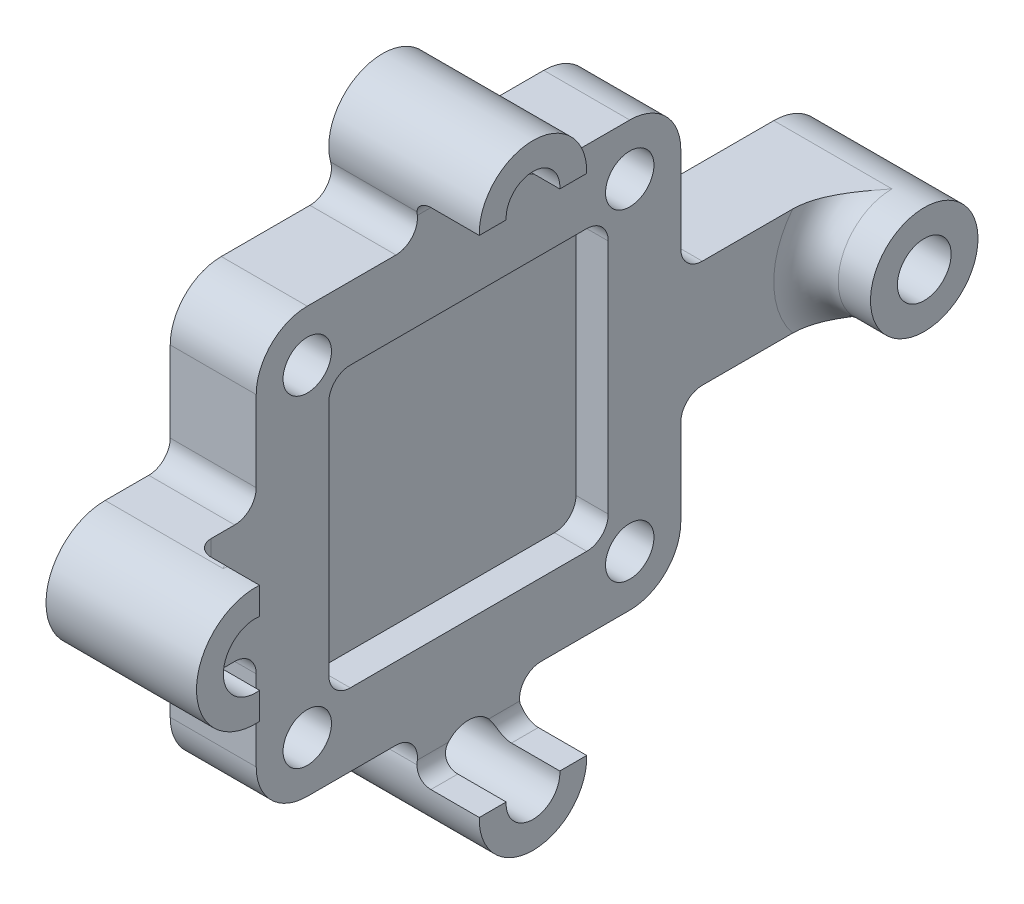
SolidWorks part; units mm, degrees
material "Beryllium S-65C, Vacuum Hot Pressed"
ref_plane "Front Plane" through (0, 0, 0) normal (1, 0, 0) x (0, 1, 0)
ref_plane "Top Plane" through (0, 0, 0) normal (0, 0, 1) x (0, 1, 0)
ref_plane "Right Plane" through (0, 0, 0) normal (0, 1, 0) x (-1, 0, 0)
sketch "Sketch1" plane through (0, 0, 0) normal (1, 0, 0) x (0, 1, 0)
sketch "Model" plane through (0, 0, 0) normal (1, 0, 0) x (0, 1, 0)
  line L0 (7, -36.4) -> (7, -53.9815)
  line L1 (-7, -36.4) -> (-7, -53.9815)
  line L2 (-7, -53.9815) -> (7, -53.9815)
  line L3 (7, -53.9815) -> (36.1014, -41.334)
  line L4 (0, 0) -> (0, -59.9211) construction
  line L5 (-7, -53.9815) -> (-36.1014, -41.334)
  line L6 (-15.7213, -20.9539) -> (-36.1014, -41.334)
  line L7 (-15.7213, -20.9539) -> (-7, -36.4)
  line L8 (15.7213, -20.9539) -> (7, -36.4)
  line L9 (36.1014, -41.334) -> (15.7213, -20.9539)
  line L10 (9.3322, 8.6384) -> (11.3322, 8.6384)
  line L11 (5.3322, 14.6384) -> (5.3322, 12.6384)
  line L12 (-5.3322, 14.6384) -> (-5.3322, 12.6384)
  line L13 (-11.3322, 8.6384) -> (-9.3322, 8.6384)
  line L14 (9.3322, -11.4697) -> (11.3322, -11.4697)
  line L15 (8.703, -13.6232) -> (10.3884, -14.7)
  line L16 (-5.3322, 14.6384) -> (5.3322, 14.6384)
  line L17 (5.3322, 12.6384) -> (-5.3322, 12.6384)
  line L18 (9.3322, -11.4697) -> (9.3322, 8.6384)
  line L19 (11.3322, 8.6384) -> (11.3322, -11.4697)
  line L20 (-5.0562, -23.046) -> (-10.3884, -14.7)
  line L21 (-10.3884, -14.7) -> (-8.703, -13.6232)
  line L22 (-8.703, -13.6232) -> (-3.3708, -21.9692)
  line L23 (-3.3708, -21.9692) -> (-5.0562, -23.046)
  line L24 (3.3708, -21.9692) -> (8.703, -13.6232)
  line L25 (10.3884, -14.7) -> (5.0562, -23.046)
  line L26 (3.3708, -21.9692) -> (5.0562, -23.046)
  line L27 (-11.3322, -11.4697) -> (-11.3322, 8.6384)
  line L28 (-9.3322, 8.6384) -> (-9.3322, -11.4697)
  line L29 (-11.3322, -11.4697) -> (-9.3322, -11.4697)
  line L30 (-7.1532, 23.5517) -> (-11.8182, 18.8569)
  line L31 (7, -36.4) -> (16.3675, -19.8094)
  line L32 (19.8245, -13.6868) -> (23.6, -7)
  line L33 (-23.6, -7) -> (-19.8245, -13.6868)
  line L34 (11.8182, 18.8569) -> (7.1532, 23.5517)
  line L35 (23.6, 7) -> (18.8366, 11.7937)
  line L36 (-16.3675, -19.8094) -> (-7, -36.4)
  line L37 (-18.8366, 11.7937) -> (-23.6, 7)
  line L38 (42.1215, -47.354) -> (36.1014, -41.334)
  line L39 (36.1014, -41.334) -> (9.7972, -52.7658)
  line L40 (7, -50.9316) -> (7, -36.4)
  line L41 (26.4236, -41.1785) -> (13.7972, -46.666)
  line L42 (18.4772, -29.3667) -> (27.0406, -37.93)
  line L43 (11.2584, -36.9935) -> (15.3215, -29.7976)
  line L44 (11, -44.8317) -> (11, -37.9769)
  line L45 (23.4176, -18.185) -> (47.354, -42.1215)
  line L46 (-36.1014, -41.334) -> (-42.1215, -47.354)
  line L47 (-7, -50.9316) -> (-7, -36.4)
  line L48 (-36.1014, -41.334) -> (-9.7972, -52.7658)
  line L49 (-11, -37.9769) -> (-11, -44.8317)
  line L50 (-15.3215, -29.7976) -> (-11.2584, -36.9935)
  line L51 (-27.0406, -37.93) -> (-18.4772, -29.3667)
  line L52 (-13.7972, -46.666) -> (-26.4236, -41.1785)
  line L53 (-47.354, -42.1215) -> (-23.4176, -18.185)
  line L54 (-23.4176, 18.185) -> (-47.354, 42.1215)
  line L55 (-42.1215, 47.354) -> (-18.185, 23.4176)
  line L56 (18.185, 23.4176) -> (42.1215, 47.354)
  line L57 (47.354, 42.1215) -> (23.4176, 18.185)
  line L58 (-26.9652, 35.0583) -> (-27.1076, 34.9484)
  line L59 (-32.6677, 40.7516) -> (-32.7868, 40.6559)
  line L60 (32.7803, 40.6611) -> (32.6631, 40.7553)
  line L61 (27.1112, 34.9456) -> (26.9658, 35.0579)
  line L62 (-33.8602, 41.9421) -> (-32.6677, 40.7516)
  line L63 (32.6631, 40.7553) -> (33.8545, 41.9467)
  arc A0 (-7, -36.4) -> (7, -36.4) centre (0, -36.4) ccw
  circle A1 centre (-15, -15) radius 2.25
  circle A2 centre (23.6, 0) radius 3
  circle A3 centre (0, -36.4) radius 3
  circle A4 centre (-15, 15) radius 2.25
  circle A5 centre (0, 25.8061) radius 3.5
  circle A6 centre (15, -15) radius 2.25
  circle A7 centre (15, 15) radius 2.25
  circle A8 centre (-23.6, 0) radius 3
  circle A9 centre (49.4975, -49.4975) radius 3
  circle A10 centre (53.9975, -49.4975) radius 1.25
  circle A11 centre (49.4975, -44.9975) radius 1.25
  circle A12 centre (49.4975, -53.9975) radius 1.25
  circle A13 centre (44.9975, -49.4975) radius 1.25
  circle A14 centre (-49.4975, -49.4975) radius 3
  circle A15 centre (-44.9975, -49.4975) radius 1.25
  circle A16 centre (-53.9975, -49.4975) radius 1.25
  circle A17 centre (-49.4975, -44.9975) radius 1.25
  circle A18 centre (-49.4975, -53.9975) radius 1.25
  circle A19 centre (-49.4975, 49.4975) radius 3
  circle A20 centre (-53.9975, 49.4975) radius 1.25
  circle A21 centre (-49.4975, 44.9975) radius 1.25
  circle A22 centre (-49.4975, 53.9975) radius 1.25
  circle A23 centre (-44.9975, 49.4975) radius 1.25
  circle A24 centre (49.4975, 49.4975) radius 3
  circle A25 centre (49.4975, 53.9975) radius 1.25
  circle A26 centre (44.9975, 49.4975) radius 1.25
  circle A27 centre (53.9975, 49.4975) radius 1.25
  circle A28 centre (49.4975, 44.9975) radius 1.25
  arc A29 (-11.8182, 18.8569) -> (-18.8366, 11.7937) centre (-15, 15) ccw
  arc A30 (-18.185, 23.4176) -> (-23.4176, 18.185) centre (-15, 15) ccw
  arc A31 (-19.8245, -13.6868) -> (-16.3675, -19.8094) centre (-15, -15) ccw
  arc A32 (-23.4176, -18.185) -> (-18.185, -23.4176) centre (-15, -15) ccw
  arc A33 (18.8366, 11.7937) -> (11.8182, 18.8569) centre (15, 15) ccw
  arc A34 (23.4176, 18.185) -> (18.185, 23.4176) centre (15, 15) ccw
  arc A35 (16.3675, -19.8094) -> (19.8245, -13.6868) centre (15, -15) ccw
  arc A36 (18.185, -23.4176) -> (23.4176, -18.185) centre (15, -15) ccw
  arc A37 (11.3322, 8.6384) -> (5.3322, 14.6384) centre (5.3322, 8.6384) ccw
  arc A38 (9.3322, 8.6384) -> (5.3322, 12.6384) centre (5.3322, 8.6384) ccw
  arc A39 (-5.3322, 14.6384) -> (-11.3322, 8.6384) centre (-5.3322, 8.6384) ccw
  arc A40 (-5.3322, 12.6384) -> (-9.3322, 8.6384) centre (-5.3322, 8.6384) ccw
  arc A41 (8.703, -13.6232) -> (9.3322, -11.4697) centre (5.3322, -11.4697) ccw
  arc A42 (10.3884, -14.7) -> (11.3322, -11.4697) centre (5.3322, -11.4697) ccw
  arc A43 (-3.3708, -21.9692) -> (3.3708, -21.9692) centre (0, -19.8157) ccw
  arc A44 (-5.0562, -23.046) -> (5.0562, -23.046) centre (0, -19.8157) ccw
  arc A45 (-11.3322, -11.4697) -> (-10.3884, -14.7) centre (-5.3322, -11.4697) ccw
  arc A46 (7.1532, 23.5517) -> (-7.1532, 23.5517) centre (0, 25.8061) ccw
  arc A47 (23.6, -7) -> (23.6, 7) centre (23.6, 0) ccw
  arc A48 (-23.6, 7) -> (-23.6, -7) centre (-23.6, 0) ccw
  arc A49 (-7, -36.4) -> (7, -36.4) centre (0, -36.4) ccw
  arc A50 (-9.3322, -11.4697) -> (-8.703, -13.6232) centre (-5.3322, -11.4697) ccw
  arc A51 (52.4421, -44.2698) -> (47.777, -42.4994) centre (49.4975, -44.9975) ccw
  arc A52 (54.5148, -46.2072) -> (52.4421, -44.2698) centre (49.4975, -49.4975) ccw
  arc A53 (54.5148, -52.7878) -> (54.5148, -46.2072) centre (53.9975, -49.4975) ccw
  arc A54 (52.4421, -54.7252) -> (54.5148, -52.7878) centre (49.4975, -49.4975) ccw
  arc A55 (46.5528, -54.7252) -> (52.4421, -54.7252) centre (49.4975, -53.9975) ccw
  arc A56 (44.4801, -52.7878) -> (46.5528, -54.7252) centre (49.4975, -49.4975) ccw
  arc A57 (42.3007, -47.5427) -> (44.4801, -52.7878) centre (44.9975, -49.4975) ccw
  arc A58 (7, -50.9316) -> (9.7972, -52.7658) centre (9, -50.9316) ccw
  arc A59 (11, -44.8317) -> (13.7972, -46.666) centre (13, -44.8317) ccw
  arc A60 (26.4236, -41.1785) -> (27.0406, -37.93) centre (25.6264, -39.3443) ccw
  arc A61 (18.4772, -29.3667) -> (15.3215, -29.7976) centre (17.063, -30.7809) ccw
  arc A62 (11.2584, -36.9935) -> (11, -37.9769) centre (13, -37.9769) ccw
  arc A63 (-44.2698, -52.4421) -> (-42.4994, -47.777) centre (-44.9975, -49.4975) ccw
  arc A64 (-46.2072, -54.5148) -> (-44.2698, -52.4421) centre (-49.4975, -49.4975) ccw
  arc A65 (-52.7878, -54.5148) -> (-46.2072, -54.5148) centre (-49.4975, -53.9975) ccw
  arc A66 (-54.7252, -52.4421) -> (-52.7878, -54.5148) centre (-49.4975, -49.4975) ccw
  arc A67 (-54.7252, -46.5528) -> (-54.7252, -52.4421) centre (-53.9975, -49.4975) ccw
  arc A68 (-52.7878, -44.4801) -> (-54.7252, -46.5528) centre (-49.4975, -49.4975) ccw
  arc A69 (-9.7972, -52.7658) -> (-7, -50.9316) centre (-9, -50.9316) ccw
  arc A70 (-13.7972, -46.666) -> (-11, -44.8317) centre (-13, -44.8317) ccw
  arc A71 (-11, -37.9769) -> (-11.2584, -36.9935) centre (-13, -37.9769) ccw
  arc A72 (-15.3215, -29.7976) -> (-18.4772, -29.3667) centre (-17.063, -30.7809) ccw
  arc A73 (-27.0406, -37.93) -> (-26.4236, -41.1785) centre (-25.6264, -39.3443) ccw
  arc A74 (-47.5427, -42.3007) -> (-52.7878, -44.4801) centre (-49.4975, -44.9975) ccw
  arc A75 (-52.4421, 44.2698) -> (-47.777, 42.4994) centre (-49.4975, 44.9975) ccw
  arc A76 (-54.5148, 46.2072) -> (-52.4421, 44.2698) centre (-49.4975, 49.4975) ccw
  arc A77 (-54.5148, 52.7878) -> (-54.5148, 46.2072) centre (-53.9975, 49.4975) ccw
  arc A78 (-52.4421, 54.7252) -> (-54.5148, 52.7878) centre (-49.4975, 49.4975) ccw
  arc A79 (-46.5528, 54.7252) -> (-52.4421, 54.7252) centre (-49.4975, 53.9975) ccw
  arc A80 (-44.4801, 52.7878) -> (-46.5528, 54.7252) centre (-49.4975, 49.4975) ccw
  arc A81 (-42.3007, 47.5427) -> (-44.4801, 52.7878) centre (-44.9975, 49.4975) ccw
  arc A82 (44.2698, 52.4421) -> (42.4994, 47.777) centre (44.9975, 49.4975) ccw
  arc A83 (46.2072, 54.5148) -> (44.2698, 52.4421) centre (49.4975, 49.4975) ccw
  arc A84 (52.7878, 54.5148) -> (46.2072, 54.5148) centre (49.4975, 53.9975) ccw
  arc A85 (54.7252, 52.4421) -> (52.7878, 54.5148) centre (49.4975, 49.4975) ccw
  arc A86 (54.7252, 46.5528) -> (54.7252, 52.4421) centre (53.9975, 49.4975) ccw
  arc A87 (52.7878, 44.4801) -> (54.7252, 46.5528) centre (49.4975, 49.4975) ccw
  arc A88 (47.5427, 42.3007) -> (52.7878, 44.4801) centre (49.4975, 44.9975) ccw
  arc A89 (35.2957, 40.7414) -> (-35.3032, 40.7349) centre (0, 0) ccw
  arc A90 (28.3951, 36.4807) -> (-28.3922, 36.483) centre (0, 0) ccw
  arc A91 (26.9658, 35.0579) -> (-26.9652, 35.0583) centre (0, 0) ccw
  arc A92 (32.432, 40.5241) -> (-32.4363, 40.5206) centre (0, 0) ccw
  spline S0 degree 2 poles (-19.9943, 14.7617) (-20.0274, 14.7948) (-20.0882, 14.8556) knots 0 0 0 0.125 0.125 0.125
  spline S1 degree 3 poles (-20.0882, 14.8556) (-20.1186, 14.886) (-20.1563, 14.9237) (-20.1994, 14.9668) knots 0.125 0.125 0.125 0.125 0.1875 0.1875 0.1875 0.1875
  spline S2 degree 3 poles (-20.1994, 14.9668) (-20.2425, 15.0099) (-20.291, 15.0584) (-20.3442, 15.1116) knots 0.1875 0.1875 0.1875 0.1875 0.25 0.25 0.25 0.25
  spline S3 degree 3 poles (-20.3442, 15.1116) (-20.4505, 15.2179) (-20.5767, 15.3441) (-20.7142, 15.4816) knots 0.25 0.25 0.25 0.25 0.375 0.375 0.375 0.375
  spline S4 degree 3 poles (-20.7142, 15.4816) (-20.8516, 15.6191) (-21.0009, 15.7683) (-21.1609, 15.9283) knots 0.375 0.375 0.375 0.375 0.5 0.5 0.5 0.5
  spline S5 degree 3 poles (-21.1609, 15.9283) (-21.3208, 16.0882) (-21.4929, 16.2603) (-21.6705, 16.438) knots 0.5 0.5 0.5 0.5 0.625 0.625 0.625 0.625
  spline S6 degree 3 poles (-21.6705, 16.438) (-21.8482, 16.6156) (-22.0322, 16.7996) (-22.2228, 16.9902) knots 0.625 0.625 0.625 0.625 0.75 0.75 0.75 0.75
  spline S7 degree 3 poles (-22.2228, 16.9902) (-22.4133, 17.1807) (-22.6118, 17.3792) (-22.8116, 17.579) knots 0.75 0.75 0.75 0.75 0.875 0.875 0.875 0.875
  spline S8 degree 3 poles (-22.8116, 17.579) (-23.0113, 17.7787) (-23.2133, 17.9807) (-23.4176, 18.185) knots 0.875 0.875 0.875 0.875 1 1 1 1
  spline S9 degree 3 poles (-18.185, 23.4176) (-17.776, 23.0086) (-17.3796, 22.6122) (-16.9943, 22.2269) knots 0 0 0 0 0.25 0.25 0.25 0.25
  spline S10 degree 3 poles (-16.9943, 22.2269) (-16.6091, 21.8417) (-16.2547, 21.4873) (-15.9312, 21.1638) knots 0.25 0.25 0.25 0.25 0.5 0.5 0.5 0.5
  spline S11 degree 3 poles (-15.9312, 21.1638) (-15.7694, 21.002) (-15.6199, 20.8525) (-15.4833, 20.7159) knots 0.5 0.5 0.5 0.5 0.625 0.625 0.625 0.625
  spline S12 degree 3 poles (-15.4833, 20.7159) (-15.3468, 20.5794) (-15.223, 20.4556) (-15.1156, 20.3482) knots 0.625 0.625 0.625 0.625 0.75 0.75 0.75 0.75
  spline S13 degree 3 poles (-15.1156, 20.3482) (-15.0081, 20.2407) (-14.9194, 20.152) (-14.8577, 20.0903) knots 0.75 0.75 0.75 0.75 0.875 0.875 0.875 0.875
  spline S14 degree 2 poles (-14.8577, 20.0903) (-14.7961, 20.0287) (-14.7617, 19.9943) knots 0.875 0.875 0.875 1 1 1
  spline S15 degree 3 poles (-15.7213, -20.9539) (-15.8911, -21.1236) (-16.0717, -21.3043) (-16.4527, -21.6853) (-16.653, -21.8856) (-17.0746, -22.3072) (-17.2928, -22.5254) (-17.7332, -22.9658) (-17.9571, -23.1896) (-18.185, -23.4176) knots 0 0 0 0 0.25 0.25 0.5 0.5 0.75 0.75 1 1 1 1
  spline S16 degree 3 poles (-23.4176, -18.185) (-23.0086, -17.776) (-22.6122, -17.3796) (-22.2269, -16.9943) knots 0 0 0 0 0.25 0.25 0.25 0.25
  spline S17 degree 3 poles (-22.2269, -16.9943) (-21.8417, -16.6091) (-21.4873, -16.2547) (-21.1638, -15.9312) knots 0.25 0.25 0.25 0.25 0.5 0.5 0.5 0.5
  spline S18 degree 3 poles (-21.1638, -15.9312) (-21.002, -15.7694) (-20.8525, -15.6199) (-20.7159, -15.4833) knots 0.5 0.5 0.5 0.5 0.625 0.625 0.625 0.625
  spline S19 degree 3 poles (-20.7159, -15.4833) (-20.5794, -15.3468) (-20.4556, -15.223) (-20.3482, -15.1156) knots 0.625 0.625 0.625 0.625 0.75 0.75 0.75 0.75
  spline S20 degree 3 poles (-20.3482, -15.1156) (-20.2407, -15.0081) (-20.152, -14.9194) (-20.0903, -14.8577) knots 0.75 0.75 0.75 0.75 0.875 0.875 0.875 0.875
  spline S21 degree 2 poles (-20.0903, -14.8577) (-20.0287, -14.7961) (-19.9943, -14.7617) knots 0.875 0.875 0.875 1 1 1
  spline S22 degree 2 poles (14.7617, 19.9943) (14.7948, 20.0274) (14.8556, 20.0882) knots 0 0 0 0.125 0.125 0.125
  spline S23 degree 3 poles (14.8556, 20.0882) (14.886, 20.1186) (14.9237, 20.1563) (14.9668, 20.1994) knots 0.125 0.125 0.125 0.125 0.1875 0.1875 0.1875 0.1875
  spline S24 degree 3 poles (14.9668, 20.1994) (15.0099, 20.2425) (15.0584, 20.291) (15.1116, 20.3442) knots 0.1875 0.1875 0.1875 0.1875 0.25 0.25 0.25 0.25
  spline S25 degree 3 poles (15.1116, 20.3442) (15.2179, 20.4505) (15.3441, 20.5767) (15.4816, 20.7142) knots 0.25 0.25 0.25 0.25 0.375 0.375 0.375 0.375
  spline S26 degree 3 poles (15.4816, 20.7142) (15.6191, 20.8516) (15.7683, 21.0009) (15.9283, 21.1609) knots 0.375 0.375 0.375 0.375 0.5 0.5 0.5 0.5
  spline S27 degree 3 poles (15.9283, 21.1609) (16.0882, 21.3208) (16.2603, 21.4929) (16.438, 21.6705) knots 0.5 0.5 0.5 0.5 0.625 0.625 0.625 0.625
  spline S28 degree 3 poles (16.438, 21.6705) (16.6156, 21.8482) (16.7996, 22.0322) (16.9902, 22.2228) knots 0.625 0.625 0.625 0.625 0.75 0.75 0.75 0.75
  spline S29 degree 3 poles (16.9902, 22.2228) (17.1807, 22.4133) (17.3792, 22.6118) (17.579, 22.8116) knots 0.75 0.75 0.75 0.75 0.875 0.875 0.875 0.875
  spline S30 degree 3 poles (17.579, 22.8116) (17.7787, 23.0113) (17.9807, 23.2133) (18.185, 23.4176) knots 0.875 0.875 0.875 0.875 1 1 1 1
  spline S31 degree 3 poles (23.4176, 18.185) (23.0086, 17.776) (22.6122, 17.3796) (22.2269, 16.9943) knots 0 0 0 0 0.25 0.25 0.25 0.25
  spline S32 degree 3 poles (22.2269, 16.9943) (21.8417, 16.6091) (21.4873, 16.2547) (21.1638, 15.9312) knots 0.25 0.25 0.25 0.25 0.5 0.5 0.5 0.5
  spline S33 degree 3 poles (21.1638, 15.9312) (21.002, 15.7694) (20.8525, 15.6199) (20.7159, 15.4833) knots 0.5 0.5 0.5 0.5 0.625 0.625 0.625 0.625
  spline S34 degree 3 poles (20.7159, 15.4833) (20.5794, 15.3468) (20.4556, 15.223) (20.3482, 15.1156) knots 0.625 0.625 0.625 0.625 0.75 0.75 0.75 0.75
  spline S35 degree 3 poles (20.3482, 15.1156) (20.2407, 15.0081) (20.152, 14.9194) (20.0903, 14.8577) knots 0.75 0.75 0.75 0.75 0.875 0.875 0.875 0.875
  spline S36 degree 2 poles (20.0903, 14.8577) (20.0287, 14.7961) (19.9943, 14.7617) knots 0.875 0.875 0.875 1 1 1
  spline S37 degree 2 poles (19.9943, -14.7617) (20.0274, -14.7948) (20.0882, -14.8556) knots 0 0 0 0.125 0.125 0.125
  spline S38 degree 3 poles (20.0882, -14.8556) (20.1186, -14.886) (20.1563, -14.9237) (20.1994, -14.9668) knots 0.125 0.125 0.125 0.125 0.1875 0.1875 0.1875 0.1875
  spline S39 degree 3 poles (20.1994, -14.9668) (20.2425, -15.0099) (20.291, -15.0584) (20.3442, -15.1116) knots 0.1875 0.1875 0.1875 0.1875 0.25 0.25 0.25 0.25
  spline S40 degree 3 poles (20.3442, -15.1116) (20.4505, -15.2179) (20.5767, -15.3441) (20.7142, -15.4816) knots 0.25 0.25 0.25 0.25 0.375 0.375 0.375 0.375
  spline S41 degree 3 poles (20.7142, -15.4816) (20.8516, -15.6191) (21.0009, -15.7683) (21.1609, -15.9283) knots 0.375 0.375 0.375 0.375 0.5 0.5 0.5 0.5
  spline S42 degree 3 poles (21.1609, -15.9283) (21.3208, -16.0882) (21.4929, -16.2603) (21.6705, -16.438) knots 0.5 0.5 0.5 0.5 0.625 0.625 0.625 0.625
  spline S43 degree 3 poles (21.6705, -16.438) (21.8482, -16.6156) (22.0322, -16.7996) (22.2228, -16.9902) knots 0.625 0.625 0.625 0.625 0.75 0.75 0.75 0.75
  spline S44 degree 3 poles (22.2228, -16.9902) (22.4133, -17.1807) (22.6118, -17.3792) (22.8116, -17.579) knots 0.75 0.75 0.75 0.75 0.875 0.875 0.875 0.875
  spline S45 degree 3 poles (22.8116, -17.579) (23.0113, -17.7787) (23.2133, -17.9807) (23.4176, -18.185) knots 0.875 0.875 0.875 0.875 1 1 1 1
  spline S46 degree 3 poles (18.185, -23.4176) (17.9577, -23.1903) (17.7344, -22.967) (17.2949, -22.5275) (17.077, -22.3096) (16.6566, -21.8892) (16.456, -21.6886) (16.0735, -21.3061) (15.8905, -21.1231) (15.7213, -20.9539) knots 0 0 0 0 0.25 0.25 0.5 0.5 0.75 0.75 1 1 1 1
  spline S47 degree 3 poles (47.777, -42.4994) (47.7283, -42.4597) (47.6308, -42.3802) (47.4897, -42.2541) (47.3993, -42.1657) (47.354, -42.1215) knots 0 0 0 0 0.332053 0.665228 1 1 1 1
  spline S48 degree 3 poles (42.1215, -47.354) (42.1519, -47.3849) (42.2128, -47.4465) (42.2712, -47.5104) (42.3007, -47.5427) knots 0 0 0 0 0.500899 1 1 1 1
  spline S49 degree 3 poles (-42.4994, -47.777) (-42.4597, -47.7283) (-42.3802, -47.6308) (-42.2541, -47.4897) (-42.1657, -47.3993) (-42.1215, -47.354) knots 0 0 0 0 0.332053 0.665228 1 1 1 1
  spline S50 degree 3 poles (-47.354, -42.1215) (-47.3849, -42.1519) (-47.4465, -42.2128) (-47.5104, -42.2712) (-47.5427, -42.3007) knots 0 0 0 0 0.500899 1 1 1 1
  spline S51 degree 3 poles (-47.777, 42.4994) (-47.7283, 42.4597) (-47.6308, 42.3802) (-47.4897, 42.2541) (-47.3993, 42.1657) (-47.354, 42.1215) knots 0 0 0 0 0.332053 0.665228 1 1 1 1
  spline S52 degree 3 poles (-42.1215, 47.354) (-42.1519, 47.3849) (-42.2128, 47.4465) (-42.2712, 47.5104) (-42.3007, 47.5427) knots 0 0 0 0 0.500899 1 1 1 1
  spline S53 degree 3 poles (42.4994, 47.777) (42.4597, 47.7283) (42.3802, 47.6308) (42.2541, 47.4897) (42.1657, 47.3993) (42.1215, 47.354) knots 0 0 0 0 0.332053 0.665228 1 1 1 1
  spline S54 degree 3 poles (47.354, 42.1215) (47.3849, 42.1519) (47.4465, 42.2128) (47.5104, 42.2712) (47.5427, 42.3007) knots 0 0 0 0 0.500899 1 1 1 1
  spline S55 degree 3 poles (-28.5315, 33.7959) (-29.7895, 35.052) (-32.0792, 37.3379) (-34.3674, 39.6223) (-35.3987, 40.652) knots 0 0 0 0 0.007511 0.013676 0.013676 0.013676 0.013676
  spline S56 degree 2 poles (-35.3987, 40.652) (-35.3686, 40.6783) (-35.3032, 40.7349) knots 0 0 0 1 1 1
  spline S57 degree 3 poles (-35.3032, 40.7349) (-35.1099, 40.6224) (-34.9092, 40.5288) (-34.4904, 40.3852) (-34.2697, 40.3351) (-33.8275, 40.2977) (-33.6003, 40.3102) (-33.1695, 40.4177) (-32.9622, 40.5144) (-32.7868, 40.6559) knots 0 0 0 0 0.25 0.25 0.5 0.5 0.75 0.75 1 1 1 1
  spline S58 degree 3 poles (-32.7868, 40.6559) (-31.862, 39.7274) (-29.9689, 37.826) (-28.0759, 35.9226) (-27.1076, 34.9484) knots 0 0 0 0 0.005544 0.01135 0.01135 0.01135 0.01135
  spline S59 degree 3 poles (-27.1076, 34.9484) (-27.2253, 34.8571) (-27.339, 34.7679) (-27.449, 34.6808) knots 0 0 0 0 0.125 0.125 0.125 0.125
  spline S60 degree 3 poles (-27.449, 34.6808) (-27.5591, 34.5937) (-27.6622, 34.5112) (-27.7562, 34.4355) knots 0.125 0.125 0.125 0.125 0.25 0.25 0.25 0.25
  spline S61 degree 3 poles (-27.7562, 34.4355) (-27.8501, 34.3598) (-27.9353, 34.2905) (-28.01, 34.2293) knots 0.25 0.25 0.25 0.25 0.375 0.375 0.375 0.375
  spline S62 degree 3 poles (-28.01, 34.2293) (-28.0847, 34.1682) (-28.1508, 34.1137) (-28.208, 34.0664) knots 0.375 0.375 0.375 0.375 0.5 0.5 0.5 0.5
  spline S63 degree 3 poles (-28.208, 34.0664) (-28.3224, 33.9716) (-28.4014, 33.9054) (-28.4542, 33.861) knots 0.5 0.5 0.5 0.5 0.75 0.75 0.75 0.75
  spline S64 degree 2 poles (-28.4542, 33.861) (-28.5069, 33.8167) (-28.5315, 33.7959) knots 0.75 0.75 0.75 1 1 1
  spline S65 degree 3 poles (-32.6677, 40.7516) (-30.7679, 38.8549) (-28.8673, 36.9573) (-26.9652, 35.0583) knots 0 0 0 0 0.011355 0.011355 0.011355 0.011355
  spline S66 degree 3 poles (26.9658, 35.0579) (28.8661, 36.9582) (30.765, 38.8572) (32.6631, 40.7553) knots 0 0 0 0 0.011354 0.011354 0.011354 0.011354
  spline S67 degree 3 poles (27.1112, 34.9456) (28.0774, 35.9208) (29.9671, 37.8268) (31.8569, 39.731) (32.7803, 40.6611) knots 0 0 0 0 0.005803 0.011349 0.011349 0.011349 0.011349
  spline S68 degree 3 poles (35.3918, 40.658) (34.3627, 39.6272) (32.0785, 37.3393) (29.7928, 35.0499) (28.5366, 33.7916) knots 0 0 0 0 0.006163 0.013675 0.013675 0.013675 0.013675
  spline S69 degree 2 poles (28.5366, 33.7916) (28.5119, 33.8125) (28.46, 33.8561) knots 0 0 0 0.25 0.25 0.25
  spline S70 degree 3 poles (28.46, 33.8561) (28.4081, 33.8998) (28.3276, 33.9673) (28.2139, 34.0615) knots 0.25 0.25 0.25 0.25 0.5 0.5 0.5 0.5
  spline S71 degree 3 poles (28.2139, 34.0615) (28.157, 34.1086) (28.0907, 34.1633) (28.0156, 34.2247) knots 0.5 0.5 0.5 0.5 0.625 0.625 0.625 0.625
  spline S72 degree 3 poles (28.0156, 34.2247) (27.9405, 34.2862) (27.857, 34.3542) (27.7624, 34.4305) knots 0.625 0.625 0.625 0.625 0.75 0.75 0.75 0.75
  spline S73 degree 3 poles (27.7624, 34.4305) (27.6678, 34.5068) (27.5654, 34.5887) (27.4554, 34.6758) knots 0.75 0.75 0.75 0.75 0.875 0.875 0.875 0.875
  spline S74 degree 3 poles (27.4554, 34.6758) (27.3453, 34.763) (27.2291, 34.8541) (27.1112, 34.9456) knots 0.875 0.875 0.875 0.875 1 1 1 1
  spline S75 degree 3 poles (32.7803, 40.6611) (32.868, 40.5904) (32.9621, 40.5316) (33.1614, 40.435) (33.2679, 40.397) (33.5926, 40.3156) (33.8191, 40.3033) (34.2611, 40.3406) (34.4783, 40.3897) (34.901, 40.5344) (35.1025, 40.6287) (35.2957, 40.7414) knots 0 0 0 0 0.125 0.125 0.25 0.25 0.5 0.5 0.75 0.75 1 1 1 1
  spline S76 degree 2 poles (35.2957, 40.7414) (35.3615, 40.6845) (35.3918, 40.658) knots 0 0 0 1 1 1
sketch "Sketch3" plane through (0, 0, 0) normal (1, 0, 0) x (0, 1, 0)
  line L0 (-15, 19.75) -> (15, 19.75)
  line L1 (-19.75, 15) -> (-19.75, -15)
  line L2 (-15, -19.75) -> (15, -19.75)
  line L3 (19.75, 15) -> (19.75, -15)
  circle A0 centre (-15, 15) radius 2.25
  circle A1 centre (15, 15) radius 2.25
  circle A2 centre (15, -15) radius 2.25
  circle A3 centre (-15, -15) radius 2.25
  arc A4 (-15, 19.75) -> (-19.75, 15) centre (-15, 15) ccw
  arc A5 (19.75, 15) -> (15, 19.75) centre (15, 15) ccw
  arc A6 (-19.75, -15) -> (-15, -19.75) centre (-15, -15) ccw
  arc A7 (15, -19.75) -> (19.75, -15) centre (15, -15) ccw
  circle A8 centre (-15, 15) radius 4.75 construction
  circle A9 centre (15, 15) radius 4.75 construction
  circle A10 centre (15, -15) radius 4.75 construction
  circle A11 centre (-15, -15) radius 4.75 construction
  dimension "D1" = 2.5
extrude "Boss-Extrude1" add sketch "Sketch3" along normal blind 3
sketch "Sketch4" plane through (0, 0, 0) normal (-1, 0, 0) x (0, -1, 0)
  line L0 (-5.5, 25.8061) -> (-5.5, 19.75)
  line L1 (-15, 19.75) -> (15, 19.75) construction
  line L2 (5.5, 25.8061) -> (5.5, 19.75)
  line L3 (5, -36.4) -> (5, -19.75)
  line L5 (15, -19.75) -> (-15, -19.75) construction
  line L6 (-5, -36.4) -> (-5.2114, -19.75)
  line L7 (-5.2114, -19.75) -> (5, -19.75)
  line L8 (-5.5, 19.75) -> (5.5, 19.75)
  circle A0 centre (0, 25.8061) radius 3.5
  circle A1 centre (-23.6, 0) radius 3
  circle A2 centre (0, -36.4) radius 3
  circle A3 centre (23.6, 0) radius 3
  circle A4 centre (0, 25.8061) radius 5.5
  circle A5 centre (-23.6, 0) radius 5
  circle A6 centre (23.6, 0) radius 5
  circle A7 centre (0, -36.4) radius 5
  line M9 (15, 19.75) -> (-15, 19.75)
  line M11 (-19.75, 15) -> (-19.75, -15)
  line M15 (19.75, -15) -> (19.75, 15)
  dimension "D1" = 2
extrude "Boss-Extrude2" add sketch "Sketch4" against normal up to surface (3 mm away) contours A6 A3 M15 | A4 A0 | A4 L0 L2 M9 | A5 A1 M11 | A7 A2 region at (0, 0, 20.1806) region at (0, 0, 31.1506) region at (0, 0, -41.2586) region at (0, 19.8835, 0) region at (0, -25.2503, -4.5781) up to face at (3, 15, -17.25)
sketch "Sketch5" plane through (3, 0, 0) normal (1, 0, 0) x (0, 1, 0)
  line L9 (-5, -36.4) -> (-5, -19.75)
  line L10 (5, -36.4) -> (5, -19.75)
  line L11 (-5, -19.75) -> (5, -19.75)
  circle A7 centre (0, -36.4) radius 5 construction
  circle A9 centre (0, -36.4) radius 5
  arc A10 (5, -36.4) -> (-5, -36.4) centre (0, -36.4) ccw
  dimension "D1" = 0
extrude "Boss-Extrude3" add sketch "Sketch5" against normal up to surface (3 mm away) up to face at (0, 0, 6.0383)
sketch "Sketch6" plane through (3, 0, 0) normal (1, 0, 0) x (0, 1, 0)
  line L4 (-13, -13) -> (-13, 13)
  line L5 (-13, 13) -> (13, 13)
  line L6 (13, 13) -> (13, -13)
  line L7 (13, -13) -> (-13, -13)
extrude "Cut-Extrude1" cut sketch "Sketch6" against normal blind 6
fillet "Fillet1" radius 2 8 edges at (1.5, 19.75, 3.1902) (1.5, 19.75, -3.1902) (1.5, -19.75, 3.1902) (1.5, -19.75, -3.1902) (1.5, -5, -19.75) (1.5, 5, -19.75) (1.5, -5.5, 19.75) (1.5, 5.5, 19.75)
fillet "Fillet2" radius 2 4 edges at (1.5, 13, -13) (1.5, -13, -13) (1.5, -13, 13) (1.5, 13, 13)
sketch "Sketch7" plane through (3, 0, 0) normal (1, 0, 0) x (0, 1, 0)
  circle A0 centre (0, 25.8061) radius 5.5
  circle A1 centre (23.6, 0) radius 5
  circle A2 centre (-23.6, 0) radius 5
  circle A3 centre (0, -36.4) radius 5
  circle A4 centre (-23.6, 0) radius 3
  circle A5 centre (0, 25.8061) radius 3.5
  circle A6 centre (23.6, 0) radius 3
  circle A7 centre (0, -36.4) radius 3
extrude "Boss-Extrude4" add sketch "Sketch7" along normal blind 6
fillet "Fillet3" radius 3 4 edges at (3, 18.6, 0) (3, 0, -31.4) (3, -18.6, 0) (3, 0, 20.3061)
sketch "Sketch8" plane through (9, 0, 0) normal (1, 0, 0) x (0, 1, 0)
  circle A0 centre (0, -36.4) radius 3 construction
  circle A1 centre (-23.6, 0) radius 3 construction
  circle A2 centre (0, 25.8061) radius 3.5 construction
  circle A3 centre (23.6, 0) radius 3 construction
  circle A4 centre (0, -36.4) radius 3
  circle A5 centre (-23.6, 0) radius 3
  circle A6 centre (0, 25.8061) radius 3.5
  circle A7 centre (23.6, 0) radius 3
  circle A8 centre (0, -36.4) radius 2.5
  circle A9 centre (-23.6, 0) radius 2.5
  circle A10 centre (0, 25.8061) radius 3
  circle A11 centre (23.6, 0) radius 2.5
  dimension "D1" = 0.5
extrude "Boss-Extrude5" add sketch "Sketch8" against normal up to surface (9 mm away) up to face at (0, 0, 0)
sketch "Sketch9" plane through (3, 0, 0) normal (1, 0, 0) x (0, 1, 0)
  line L1 (-23.4462, 25.4449) -> (23.4462, 25.4449)
  line L2 (-23.4462, 25.4449) -> (-23.4462, -25.4449)
  line L3 (-23.4462, -25.4449) -> (23.4462, -25.4449)
  line L4 (23.4462, 25.4449) -> (23.4462, -25.4449)
  line L5 (-23.4462, 25.4449) -> (23.4462, -25.4449) construction
  line L6 (-23.4462, -25.4449) -> (23.4462, 25.4449) construction
  point P0 (0, 0)
sketch "Sketch10" plane through (9, 0, 0) normal (1, 0, 0) x (0, 1, 0)
  line L0 (-23.4462, -25.4449) -> (23.4462, -25.4449) construction
  line L1 (-23.4462, 25.4449) -> (-23.4462, -25.4449) construction
  line L2 (-23.4462, 25.4449) -> (23.4462, 25.4449) construction
  line L3 (23.4462, 25.4449) -> (23.4462, -25.4449) construction
  line L4 (-23.4462, -25.4449) -> (23.4462, -25.4449)
  line L5 (-23.4462, 25.4449) -> (-23.4462, -25.4449)
  line L6 (-23.4462, 25.4449) -> (23.4462, 25.4449)
  line L7 (23.4462, 25.4449) -> (23.4462, -25.4449)
extrude "Cut-Extrude2" cut sketch "Sketch10" against normal up to surface (6 mm away) up to face at (3, 0, -2.908)
fillet "Fillet4" radius 1.5 6 edges at (3, 23.4462, -3.7464) (3, 23.4462, 3.7464) (3, 4.2391, 25.4449) (3, -4.2391, 25.4449) (3, -23.4462, -3.7464) (3, -23.4462, 3.7464)
sketch "Sketch11" plane through (0, 0, 0) normal (-1, 0, 0) x (0, -1, 0)
  line L12 (15, 19.75) -> (7.5, 19.75)
  line L13 (5.5, 21.75) -> (5.5, 25.8061)
  line L14 (-5.5, 25.8061) -> (-5.5, 21.75)
  line L15 (-7.5, 19.75) -> (-15, 19.75)
  line L16 (-19.75, 15) -> (-19.75, 6.7511)
  line L17 (-19.75, -6.7511) -> (-19.75, -15)
  line L18 (-15, -19.75) -> (-7, -19.75)
  line L19 (-5, -21.75) -> (-5, -36.4)
  line L20 (5, -36.4) -> (5, -21.75)
  line L21 (7, -19.75) -> (15, -19.75)
  line L22 (19.75, -15) -> (19.75, -6.7511)
  line L23 (19.75, 6.7511) -> (19.75, 15)
  line L24 (15, 19.75) -> (7.5, 19.75)
  line L25 (5.5, 21.75) -> (5.5, 25.8061)
  line L26 (-5.5, 25.8061) -> (-5.5, 21.75)
  line L27 (-7.5, 19.75) -> (-15, 19.75)
  line L28 (-19.75, 15) -> (-19.75, 6.7511)
  line L29 (-19.75, -6.7511) -> (-19.75, -15)
  line L30 (-15, -19.75) -> (-7, -19.75)
  line L31 (-5, -21.75) -> (-5, -36.4)
  line L32 (5, -36.4) -> (5, -21.75)
  line L33 (7, -19.75) -> (15, -19.75)
  line L34 (19.75, -15) -> (19.75, -6.7511)
  line L35 (19.75, 6.7511) -> (19.75, 15)
  circle A0 centre (0, -36.4) radius 2.5 construction
  circle A1 centre (15, -15) radius 2.25 construction
  circle A2 centre (-15, -15) radius 2.25 construction
  circle A3 centre (-15, 15) radius 2.25 construction
  circle A4 centre (15, 15) radius 2.25 construction
  circle A5 centre (23.6, 0) radius 2.5 construction
  circle A6 centre (0, 25.8061) radius 3 construction
  circle A7 centre (-23.6, 0) radius 2.5 construction
  circle A8 centre (0, -36.4) radius 2.5
  circle A9 centre (15, -15) radius 2.25
  circle A10 centre (-15, -15) radius 2.25
  circle A11 centre (-15, 15) radius 2.25
  circle A12 centre (15, 15) radius 2.25
  circle A13 centre (23.6, 0) radius 2.5
  circle A14 centre (0, 25.8061) radius 3
  circle A15 centre (-23.6, 0) radius 2.5
  arc A16 (19.75, 15) -> (15, 19.75) centre (15, 15) ccw
  arc A17 (5.5, 21.75) -> (7.5, 19.75) centre (7.5, 21.75) ccw
  arc A18 (5.5, 25.8061) -> (-5.5, 25.8061) centre (0, 25.8061) ccw
  arc A19 (-7.5, 19.75) -> (-5.5, 21.75) centre (-7.5, 21.75) ccw
  arc A20 (-15, 19.75) -> (-19.75, 15) centre (-15, 15) ccw
  arc A21 (-22.2786, 4.8222) -> (-19.75, 6.7511) centre (-21.75, 6.7511) ccw
  arc A22 (-22.2786, 4.8222) -> (-22.2786, -4.8222) centre (-23.6, 0) ccw
  arc A23 (-19.75, -6.7511) -> (-22.2786, -4.8222) centre (-21.75, -6.7511) ccw
  arc A24 (-19.75, -15) -> (-15, -19.75) centre (-15, -15) ccw
  arc A25 (-5, -21.75) -> (-7, -19.75) centre (-7, -21.75) ccw
  arc A26 (-5, -36.4) -> (5, -36.4) centre (0, -36.4) ccw
  arc A27 (7, -19.75) -> (5, -21.75) centre (7, -21.75) ccw
  arc A28 (15, -19.75) -> (19.75, -15) centre (15, -15) ccw
  arc A29 (22.2786, -4.8222) -> (19.75, -6.7511) centre (21.75, -6.7511) ccw
  arc A30 (22.2786, -4.8222) -> (22.2786, 4.8222) centre (23.6, 0) ccw
  arc A31 (19.75, 6.7511) -> (22.2786, 4.8222) centre (21.75, 6.7511) ccw
  arc A32 (19.75, 15) -> (15, 19.75) centre (15, 15) ccw
  arc A33 (5.5, 21.75) -> (7.5, 19.75) centre (7.5, 21.75) ccw
  arc A34 (5.5, 25.8061) -> (-5.5, 25.8061) centre (0, 25.8061) ccw
  arc A35 (-7.5, 19.75) -> (-5.5, 21.75) centre (-7.5, 21.75) ccw
  arc A36 (-15, 19.75) -> (-19.75, 15) centre (-15, 15) ccw
  arc A37 (-22.2786, 4.8222) -> (-19.75, 6.7511) centre (-21.75, 6.7511) ccw
  arc A38 (-22.2786, 4.8222) -> (-22.2786, -4.8222) centre (-23.6, 0) ccw
  arc A39 (-19.75, -6.7511) -> (-22.2786, -4.8222) centre (-21.75, -6.7511) ccw
  arc A40 (-19.75, -15) -> (-15, -19.75) centre (-15, -15) ccw
  arc A41 (-5, -21.75) -> (-7, -19.75) centre (-7, -21.75) ccw
  arc A42 (-5, -36.4) -> (5, -36.4) centre (0, -36.4) ccw
  arc A43 (7, -19.75) -> (5, -21.75) centre (7, -21.75) ccw
  arc A44 (15, -19.75) -> (19.75, -15) centre (15, -15) ccw
  arc A45 (22.2786, -4.8222) -> (19.75, -6.7511) centre (21.75, -6.7511) ccw
  arc A46 (22.2786, -4.8222) -> (22.2786, 4.8222) centre (23.6, 0) ccw
  arc A47 (19.75, 6.7511) -> (22.2786, 4.8222) centre (21.75, 6.7511) ccw
  dimension "D1" = 0
extrude "Boss-Extrude6" add sketch "Sketch11" along normal blind 5
sketch "Sketch13" plane through (-5, 0, 0) normal (-1, 0, 0) x (0, -1, 0)
  circle A2 centre (0, 25.8061) radius 2.5
  circle A3 centre (0, 25.8061) radius 2.5
  circle A5 centre (0, 25.8061) radius 3.5
  circle A6 centre (0, 25.8061) radius 3.5
  dimension "D1" = 0.5
  dimension "D2" = 0.5
extrude "Boss-Extrude7" add sketch "Sketch13" against normal up to surface (8 mm away) up to face at (3, 0, 1.0613)
